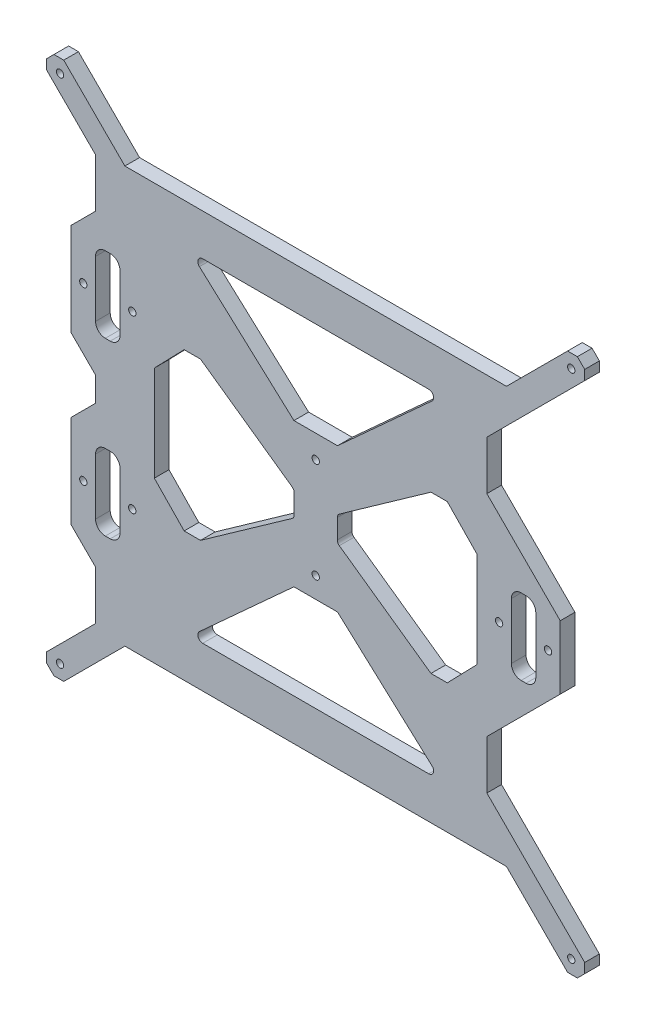
SolidWorks part; units mm, degrees
ref_plane "Piano frontale" through (0, 0, 0) normal (0, 0, 1) x (1, 0, 0)
ref_plane "Piano superiore" through (0, 0, 0) normal (0, 1, 0) x (1, 0, 0)
ref_plane "Piano destro" through (0, 0, 0) normal (1, 0, 0) x (0, 0, -1)
sketch "FRAME" plane through (0, 0, 0) normal (0, 0, 1) x (1, 0, 0)
  line L38 (65, 325) -> (63, 325)
  line L39 (63, 325) -> (60, 322)
  line L40 (60, 322) -> (60, 320)
  line L41 (60, 320) -> (60, 318)
  line L42 (60, 318) -> (80, 298)
  line L43 (80, 298) -> (80, 278)
  line L44 (80, 278) -> (70, 268)
  line L45 (70, 162) -> (80, 152)
  line L46 (60, 112) -> (80, 132)
  line L47 (80, 132) -> (80, 152)
  line L48 (60, 112) -> (60, 108)
  line L49 (60, 108) -> (63, 105)
  line L50 (63, 105) -> (65, 105)
  line L51 (275, 105) -> (277, 105)
  line L52 (277, 105) -> (280, 108)
  line L53 (280, 321) -> (280, 322)
  line L54 (280, 322) -> (277, 325)
  line L55 (280, 318) -> (240, 278)
  line L56 (270, 228) -> (260, 238)
  line L57 (260, 238) -> (240, 258)
  line L58 (240, 258) -> (240, 278)
  line L59 (270, 202) -> (260, 192)
  line L60 (260, 192) -> (240, 172)
  line L61 (280, 112) -> (260, 132)
  line L62 (260, 132) -> (240, 152)
  line L63 (240, 152) -> (240, 172)
  line L64 (273, 325) -> (250, 302)
  line L65 (161.2166, 218.9648) -> (161.2166, 211.0352)
  line L66 (122.4711, 279.6004) -> (161.1147, 244.4358)
  line L67 (161.1147, 244.4358) -> (178.9347, 244.4358)
  line L68 (273, 105) -> (248, 130)
  line L69 (104.0376, 234.4981) -> (104.0376, 195.5019)
  line L70 (92, 300) -> (248, 300)
  line L71 (92, 130) -> (248, 130)
  line L72 (70, 230) -> (80, 220)
  line L73 (80, 220) -> (80, 210)
  line L74 (80, 210) -> (70, 200)
  line L75 (104.0376, 234.4981) -> (116.2302, 247.0905)
  line L76 (116.2302, 247.0905) -> (122.9095, 247.0905)
  line L77 (122.9095, 247.0905) -> (160.3714, 220.5977)
  line L78 (217.1399, 247.0905) -> (179.678, 220.5977)
  line L79 (223.8192, 247.0905) -> (217.1399, 247.0905)
  line L80 (236.0117, 234.4981) -> (223.8192, 247.0905)
  line L81 (236.0117, 234.4981) -> (236.0117, 195.5019)
  line L82 (236.0117, 195.5019) -> (223.8192, 182.9095)
  line L83 (223.8192, 182.9095) -> (217.1399, 182.9095)
  line L84 (217.1399, 182.9095) -> (179.678, 209.4023)
  line L85 (178.8328, 218.9648) -> (178.8328, 211.0352)
  line L86 (122.9095, 182.9095) -> (160.3714, 209.4023)
  line L87 (104.0376, 195.5019) -> (116.2302, 182.9095)
  line L88 (116.2302, 182.9095) -> (122.9095, 182.9095)
  line L89 (123.8171, 283.0796) -> (216.2322, 283.0796)
  line L90 (217.5783, 279.6004) -> (178.9347, 244.4358)
  line L91 (65, 325) -> (67, 325)
  line L92 (277, 325) -> (273, 325)
  line L93 (280, 321) -> (280, 318)
  line L94 (280, 112) -> (280, 108)
  line L95 (273, 105) -> (275, 105)
  line L96 (67, 105) -> (65, 105)
  line L97 (217.5783, 150.3996) -> (178.9347, 185.5642)
  line L98 (250, 302) -> (248, 300)
  line L99 (161.1147, 185.5642) -> (178.9347, 185.5642)
  line L100 (67, 325) -> (92, 300)
  line L101 (122.4711, 150.3996) -> (161.1147, 185.5642)
  line L102 (123.8171, 146.9204) -> (216.2322, 146.9204)
  line L103 (67, 105) -> (92, 130)
  line L175 (70, 268) -> (70, 230)
  line L176 (70, 200) -> (70, 162)
  line L177 (270, 228) -> (270, 202)
  line L184 (80, 169) -> (80, 192)
  line L185 (84, 196) -> (86, 196)
  line L186 (90, 192) -> (90, 169)
  line L187 (86, 165) -> (84, 165)
  line L188 (80, 239.007) -> (80, 262.007)
  line L189 (84, 266.007) -> (86, 266.007)
  line L190 (90, 262.007) -> (90, 239.007)
  line L191 (86, 235.007) -> (84, 235.007)
  line L192 (250, 202.8629) -> (250, 225.8629)
  line L193 (254, 229.8629) -> (256, 229.8629)
  line L194 (260, 225.8629) -> (260, 202.8629)
  line L195 (256, 198.8629) -> (254, 198.8629)
  line L201 (80, 215) -> (297.8607, 215) construction
  line L202 (170.0247, 235) -> (170.0247, 194) construction
  circle A6 centre (75, 250) radius 1.5
  circle A7 centre (95.0376, 250) radius 1.5
  circle A8 centre (75, 180) radius 1.5
  circle A9 centre (95, 180) radius 1.5
  circle A10 centre (265, 215) radius 1.5
  circle A11 centre (245, 215) radius 1.5
  circle A12 centre (65.5, 319.5) radius 1.5
  circle A13 centre (274.5, 110.5) radius 1.5
  circle A14 centre (274.5, 319.5) radius 1.5
  circle A15 centre (65.5, 110.5) radius 1.5
  arc A22 (84, 196) -> (80, 192) centre (84, 192) ccw
  arc A23 (90, 192) -> (86, 196) centre (86, 192) ccw
  arc A24 (80, 169) -> (84, 165) centre (84, 169) ccw
  arc A25 (86, 165) -> (90, 169) centre (86, 169) ccw
  circle A36 centre (170.0247, 194) radius 1.5
  circle A37 centre (170.0247, 235) radius 1.5
  arc A38 (86, 235.007) -> (90, 239.007) centre (86, 239.007) ccw
  arc A39 (84, 266.007) -> (80, 262.007) centre (84, 262.007) ccw
  arc A40 (90, 262.007) -> (86, 266.007) centre (86, 262.007) ccw
  arc A41 (80, 239.007) -> (84, 235.007) centre (84, 239.007) ccw
  arc A42 (256, 198.8629) -> (260, 202.8629) centre (256, 202.8629) ccw
  arc A43 (254, 229.8629) -> (250, 225.8629) centre (254, 225.8629) ccw
  arc A44 (260, 225.8629) -> (256, 229.8629) centre (256, 225.8629) ccw
  arc A45 (250, 202.8629) -> (254, 198.8629) centre (254, 202.8629) ccw
  arc A48 (122.4711, 279.6004) -> (123.8171, 283.0796) centre (123.8171, 281.0796) cw
  arc A49 (123.8171, 146.9204) -> (122.4711, 150.3996) centre (123.8171, 148.9204) cw
  arc A52 (217.5783, 279.6004) -> (216.2322, 283.0796) centre (216.2322, 281.0796) ccw
  arc A53 (216.2322, 146.9204) -> (217.5783, 150.3996) centre (216.2322, 148.9204) ccw
  arc A54 (178.8328, 218.9648) -> (179.678, 220.5977) centre (180.8328, 218.9648) cw
  arc A55 (178.8328, 211.0352) -> (179.678, 209.4023) centre (180.8328, 211.0352) ccw
  arc A56 (161.2166, 218.9648) -> (160.3714, 220.5977) centre (159.2166, 218.9648) ccw
  arc A57 (160.3714, 209.4023) -> (161.2166, 211.0352) centre (159.2166, 211.0352) ccw
  point P105 (236.0117, 215)
  point P112 (104.0376, 215)
  point P117 (170.0247, 244.4358)
  point P118 (170.0247, 283.0796)
  point P301 (118.6476, 283.0796)
  point P320 (118.6476, 146.9204)
  point P323 (221.4017, 283.0796)
  point P326 (221.4017, 146.9204)
  point P329 (178.8328, 220)
  point P332 (178.8328, 210)
  point P335 (161.2166, 220)
  point P338 (161.2166, 210)
  dimension "D1" = 2
  dimension "D3" = 2
  dimension "D4" = 2
  dimension "D5" = 2
  dimension "D6" = 2
  dimension "D7" = 2
sketch "ANCORS" [suppressed] plane through (0, 0, 0) normal (0, 0, 1) x (1, 0, 0)
  line L1 (170.0247, 235) -> (170.0247, 194) construction
  line L2 (170.0247, 214.5) -> (158.9936, 214.5) construction
  circle A0 centre (120.7826, 212.556) radius 2
  circle A1 centre (216.1502, 212.556) radius 2
  circle A2 centre (167.2683, 270.0641) radius 2
  circle A3 centre (167.2683, 156.9648) radius 2
  circle A4 centre (120.7826, 90.4425) radius 2
  circle A5 centre (216.1502, 90.4425) radius 2
  circle A6 centre (170.0247, 214.5) radius 2
  dimension "D1" = 4
extrude "Boss-Extrude1" add sketch "FRAME" along normal blind 6
